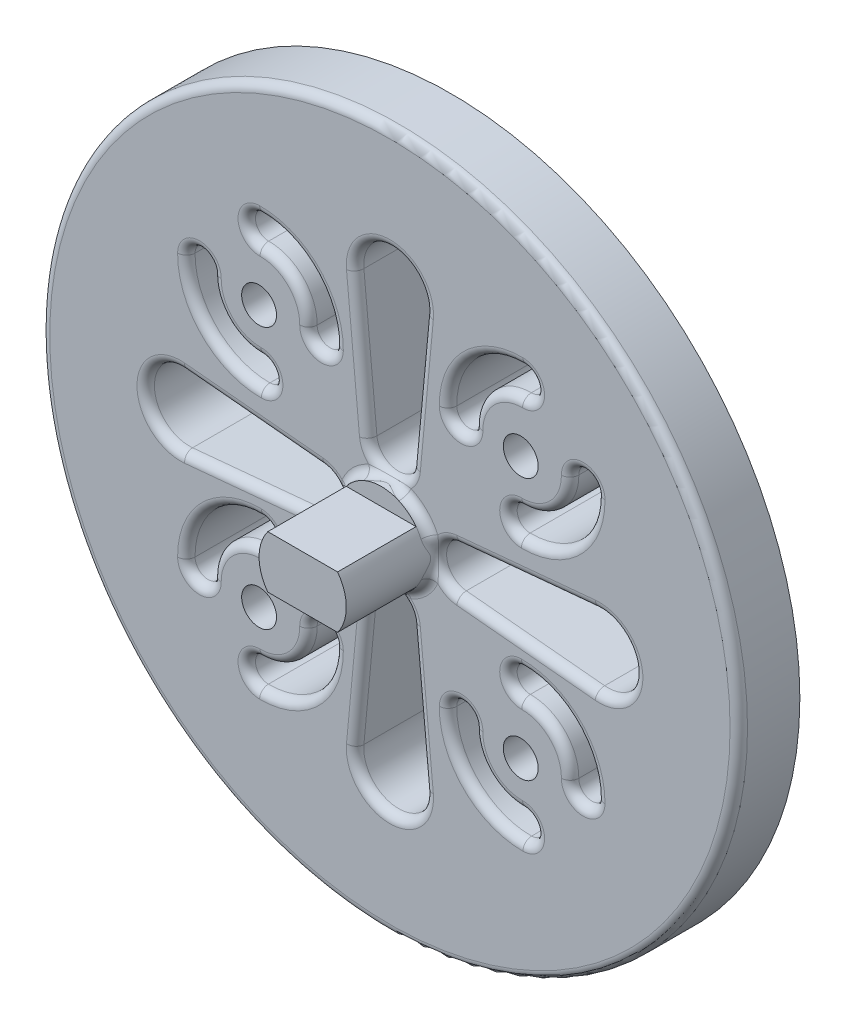
SolidWorks part; units mm, degrees
material "Cast Alloy Steel"
ref_plane "Front Plane" through (0, 0, 0) normal (0, 0, 1) x (1, 0, 0)
ref_plane "Top Plane" through (0, 0, 0) normal (0, 1, 0) x (1, 0, 0)
ref_plane "Right Plane" through (0, 0, 0) normal (1, 0, 0) x (0, 0, -1)
sketch "Sketch2" plane through (0, 0, 0) normal (1, 0, 0) x (0, 0, -1)
  line L0 (0, 0) -> (0, 20)
  line L1 (0, 20) -> (2, 20)
  line L3 (2, 17) -> (5, 17)
  line L4 (5, 17) -> (5, 0)
  line L5 (0, 0) -> (5, 0)
  line L6 (2, 20) -> (3.5, 20)
  line L7 (3.5, 20) -> (3.5, 18.5)
  line L8 (3.5, 18.5) -> (2, 18.5)
  line L9 (2, 18.5) -> (2, 17)
  dimension "D1" = 2
  dimension "D2" = 3
  dimension "D3" = 3
  dimension "D4" = 20
  dimension "D5" = 17
  dimension "D6" = 1.5
revolve "Revolve1" add sketch "Sketch2" angle 360 about L5 region at (0, 9.4028, -2.4095)
sketch "Sketch3" plane through (0, 0, -5) normal (0, 0, -1) x (-1, 0, 0)
  line L1 (7.5, -7.5) -> (-7.5, -7.5) construction
  line L2 (7.5, -7.5) -> (7.5, 7.5) construction
  line L3 (7.5, 7.5) -> (-7.5, 7.5) construction
  line L4 (-7.5, -7.5) -> (-7.5, 7.5) construction
  line L5 (7.5, -7.5) -> (-7.5, 7.5) construction
  line L6 (7.5, 7.5) -> (-7.5, -7.5) construction
  circle A0 centre (-7.5, 7.5) radius 1
  circle A1 centre (7.5, 7.5) radius 1
  circle A2 centre (7.5, -7.5) radius 1
  circle A3 centre (-7.5, -7.5) radius 1
  point P0 (0, 0)
  dimension "D2" = 2
  dimension "D1" = 15
extrude "Cut-Extrude1" cut sketch "Sketch3" against normal blind 20
sketch "Sketch4" plane through (0, 0, 0) normal (0, 0, 1) x (1, 0, 0)
  line L0 (0, 0) -> (0, 12) construction
  line L1 (-1.9912, 11.8125) -> (-1.2445, 3.8828)
  line L2 (1.2445, 3.8828) -> (1.9912, 11.8125)
  line L3 (3.8828, -1.2445) -> (11.8125, -1.9912)
  line L4 (11.8125, 1.9912) -> (3.8828, 1.2445)
  line L5 (-1.2445, -3.8828) -> (-1.9912, -11.8125)
  line L6 (1.9912, -11.8125) -> (1.2445, -3.8828)
  line L7 (-3.8828, 1.2445) -> (-11.8125, 1.9912)
  line L8 (-11.8125, -1.9912) -> (-3.8828, -1.2445)
  arc A0 (-1.9912, 11.8125) -> (1.9912, 11.8125) centre (0, 12) cw
  arc A1 (-1.2445, 3.8828) -> (1.2445, 3.8828) centre (0, 4) ccw
  arc A2 (11.8125, 1.9912) -> (11.8125, -1.9912) centre (12, 0) cw
  arc A3 (3.8828, 1.2445) -> (3.8828, -1.2445) centre (4, 0) ccw
  arc A4 (1.9912, -11.8125) -> (-1.9912, -11.8125) centre (0, -12) cw
  arc A5 (1.2445, -3.8828) -> (-1.2445, -3.8828) centre (0, -4) ccw
  arc A6 (-11.8125, -1.9912) -> (-11.8125, 1.9912) centre (-12, 0) cw
  arc A7 (-3.8828, -1.2445) -> (-3.8828, 1.2445) centre (-4, 0) ccw
  point P29 (0, 0)
  dimension "D3" = 2
  dimension "D4" = 1.25
  dimension "D1" = 12
  dimension "D2" = 4
  dimension "D5" = 4
extrude "Cut-Extrude2" cut sketch "Sketch4" against normal blind 20
fillet "Fillet2" radius 0.5 16 edges at (-1.6178, -7.8477, 0) (0, -2.75, 0) (1.6178, -7.8477, 0) (7.8477, -1.6178, 0) (2.75, 0, 0) (7.8477, 1.6178, 0) (1.6178, 7.8477, 0) (0, 2.75, 0) (-1.6178, 7.8477, 0) (-7.8477, 1.6178, 0) (-2.75, 0, 0) (-7.8477, -1.6178, 0) (0, -14, 0) (14, 0, 0) (0, 14, 0) (-14, 0, 0)
fillet "Fillet3" radius 0.5 1 edges at (20, 0, 0)
sketch "Sketch5" plane through (0, 0, 0) normal (0, 0, 1) x (1, 0, 0)
  circle A0 centre (0, 0) radius 2.5
  dimension "D1" = 5
extrude "Boss-Extrude2" add sketch "Sketch5" along normal blind 5 and the other way blind 1
sketch "Sketch7" plane through (0, 0, 5) normal (0, 0, 1) x (1, 0, 0)
  line L0 (-2, 1.5) -> (2, 1.5)
  line L2 (-2, -1.5) -> (2, -1.5)
  arc A0 (-2, -1.5) -> (2, -1.5) centre (0, 0) ccw
  arc A1 (2, 1.5) -> (-2, 1.5) centre (0, 0) ccw
  dimension "D2" = 5
  dimension "D1" = 4
extrude "Cut-Extrude3" cut sketch "Sketch7" against normal blind 4.5
fillet "Fillet4" radius 0.5 8 edges at (-0.0737, 2.4989, -0.0653) (1.7678, 1.7678, 0) (2.4989, 0.0737, -0.0653) (1.7678, -1.7678, 0) (0.0737, -2.4989, -0.0653) (-1.7678, -1.7678, 0) (-2.4989, -0.0737, -0.0653) (-1.7678, 1.7678, 0)
sketch "Sketch8" plane through (0, 0, 0) normal (0, 0, 1) x (1, 0, 0)
  line L0 (-7.4203, 8.6993) -> (-7.4203, 6.6993) construction
  line L1 (0.0797, 0.1993) -> (-7.4203, 7.6993) construction
  line L2 (-7.4203, 7.6993) -> (-4.9454, 10.1741) construction
  arc A0 (-7.456, 11.1991) -> (-3.9205, 7.6636) centre (-7.4203, 7.6993) cw construction
  arc A1 (-7.4484, 10.4491) -> (-4.6704, 7.6712) centre (-7.4203, 7.6993) cw
  arc A2 (-7.4637, 11.9491) -> (-3.1705, 7.6559) centre (-7.4203, 7.6993) cw
  arc A3 (-7.4484, 10.4491) -> (-7.4637, 11.9491) centre (-7.456, 11.1991) cw
  arc A4 (-4.6704, 7.6712) -> (-3.1705, 7.6559) centre (-3.9205, 7.6636) ccw
  arc A5 (-10.1701, 7.7273) -> (-7.3922, 4.9494) centre (-7.4203, 7.6993) ccw
  arc A6 (-10.1701, 7.7273) -> (-11.6701, 7.7426) centre (-10.9201, 7.735) ccw
  arc A7 (-11.6701, 7.7426) -> (-7.3769, 3.4495) centre (-7.4203, 7.6993) ccw
  arc A8 (-7.3922, 4.9494) -> (-7.3769, 3.4495) centre (-7.3846, 4.1995) cw
  arc A9 (7.6078, 10.4491) -> (4.8299, 7.6712) centre (7.5797, 7.6993) ccw
  arc A10 (4.8299, 7.6712) -> (3.3299, 7.6559) centre (4.0799, 7.6636) cw
  arc A11 (7.6231, 11.9491) -> (3.3299, 7.6559) centre (7.5797, 7.6993) ccw
  arc A12 (7.6078, 10.4491) -> (7.6231, 11.9491) centre (7.6154, 11.1991) ccw
  arc A13 (7.5516, 4.9494) -> (7.5363, 3.4495) centre (7.544, 4.1995) ccw
  arc A14 (11.8295, 7.7426) -> (7.5363, 3.4495) centre (7.5797, 7.6993) cw
  arc A15 (10.3296, 7.7273) -> (11.8295, 7.7426) centre (11.0795, 7.735) cw
  arc A16 (10.3296, 7.7273) -> (7.5516, 4.9494) centre (7.5797, 7.6993) cw
  arc A17 (10.3296, -7.3288) -> (7.5516, -4.5509) centre (7.5797, -7.3007) ccw
  arc A18 (7.5516, -4.5509) -> (7.5363, -3.0509) centre (7.544, -3.8009) cw
  arc A19 (11.8295, -7.3441) -> (7.5363, -3.0509) centre (7.5797, -7.3007) ccw
  arc A20 (10.3296, -7.3288) -> (11.8295, -7.3441) centre (11.0795, -7.3364) ccw
  arc A21 (4.8299, -7.2727) -> (3.3299, -7.2574) centre (4.0799, -7.265) ccw
  arc A22 (7.6231, -11.5505) -> (3.3299, -7.2574) centre (7.5797, -7.3007) cw
  arc A23 (7.6078, -10.0506) -> (7.6231, -11.5505) centre (7.6154, -10.8005) cw
  arc A24 (7.6078, -10.0506) -> (4.8299, -7.2727) centre (7.5797, -7.3007) cw
  arc A25 (-7.4484, -10.0506) -> (-4.6704, -7.2727) centre (-7.4203, -7.3007) ccw
  arc A26 (-4.6704, -7.2727) -> (-3.1705, -7.2574) centre (-3.9205, -7.265) cw
  arc A27 (-7.4637, -11.5505) -> (-3.1705, -7.2574) centre (-7.4203, -7.3007) ccw
  arc A28 (-7.4484, -10.0506) -> (-7.4637, -11.5505) centre (-7.456, -10.8005) ccw
  arc A29 (-7.3922, -4.5509) -> (-7.3769, -3.0509) centre (-7.3846, -3.8009) ccw
  arc A30 (-11.6701, -7.3441) -> (-7.3769, -3.0509) centre (-7.4203, -7.3007) cw
  arc A31 (-10.1701, -7.3288) -> (-11.6701, -7.3441) centre (-10.9201, -7.3364) cw
  arc A32 (-10.1701, -7.3288) -> (-7.3922, -4.5509) centre (-7.4203, -7.3007) cw
  point P63 (0.0797, 0.1993)
  dimension "D1" = 3.5
  dimension "D2" = 5
extrude "Cut-Extrude4" cut sketch "Sketch8" against normal blind 10
fillet "Fillet5" radius 0.5 32 edges at (-10.9125, -8.0864, 0) (-10.4255, -4.2955, 0) (-6.6346, -3.8086, 0) (-8.206, -10.7929, 0) (-5.4757, -9.2453, 0) (-3.9281, -6.5151, 0) (8.3654, -10.7929, 0) (4.5745, -10.3059, 0) (4.0875, -6.5151, 0) (11.0719, -8.0864, 0) (9.5243, -5.3562, 0) (6.794, -3.8086, 0) (6.794, 4.2071, 0) (9.5243, 5.7547, 0) (11.0719, 8.4849, 0) (4.0875, 6.9136, 0) (4.5745, 10.7045, 0) (8.3654, 11.1914, 0) (-6.6346, 4.2071, 0) (-10.4255, 4.6941, 0) (-10.9125, 8.4849, 0) (-3.9281, 6.9136, 0) (-5.4757, 9.6438, 0) (-8.206, 11.1914, 0) (-9.3648, -5.3562, 0) (-4.4151, -10.3059, 0) (5.6352, -9.2453, 0) (10.5849, -4.2955, 0) (10.5849, 4.6941, 0) (5.6352, 9.6438, 0) (-9.3648, 5.7547, 0) (-4.4151, 10.7045, 0)
